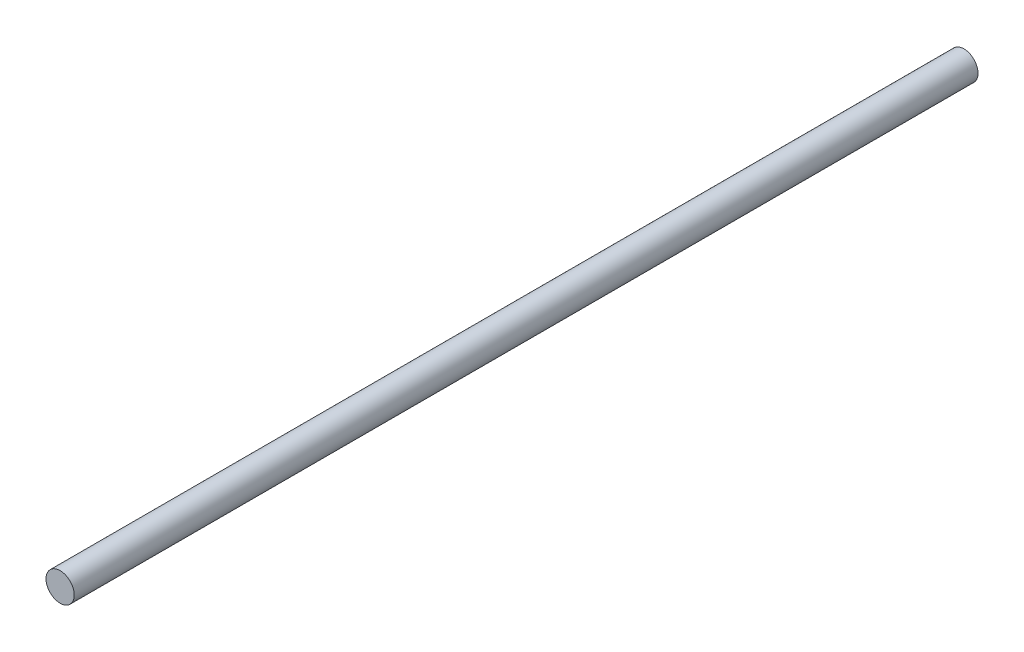
SolidWorks part; units mm, degrees
material "AISI 1035 Steel (SS)"
ref_plane "Front Plane" through (0, 0, 0) normal (0, 0, 1) x (1, 0, 0)
ref_plane "Top Plane" through (0, 0, 0) normal (0, 1, 0) x (1, 0, 0)
ref_plane "Right Plane" through (0, 0, 0) normal (1, 0, 0) x (0, 0, -1)
sketch "Sketch2" plane through (0, 0, 0) normal (0, 0, 1) x (1, 0, 0)
  circle A0 centre (0, 0) radius 4.7625
  dimension "D1" = 9.525
extrude "Boss-Extrude1" add sketch "Sketch2" along normal blind 304.8
